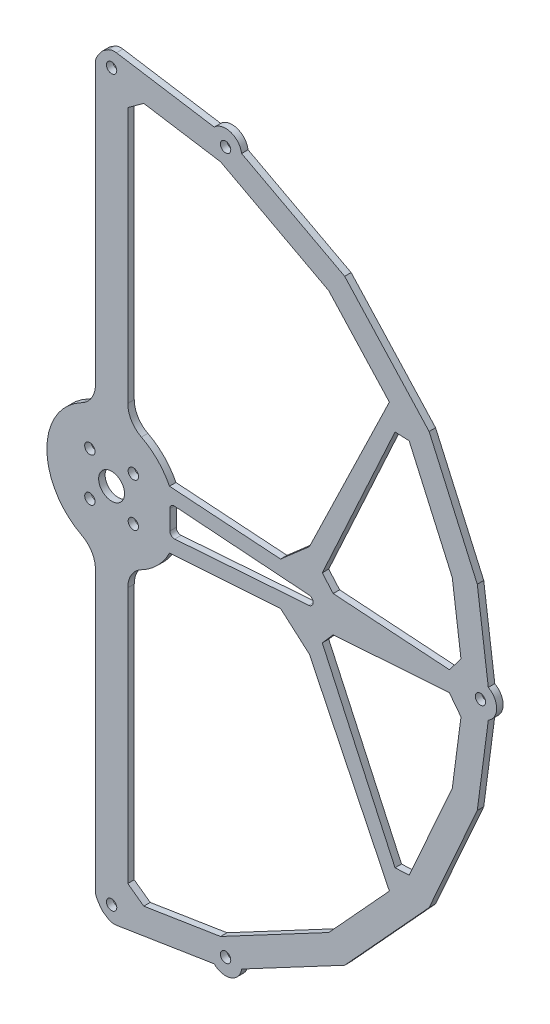
SolidWorks part; units mm, degrees
material "碳纤维板_1600kg_m3"
ref_plane "前视基准面" through (0, 0, 0) normal (0, 0, 1) x (1, 0, 0)
ref_plane "上视基准面" through (0, 0, 0) normal (0, 1, 0) x (1, 0, 0)
ref_plane "右视基准面" through (0, 0, 0) normal (1, 0, 0) x (0, 0, -1)
other "Configuration Table"
sketch "草图1" plane through (0, 0, 0) normal (0, 0, 1) x (1, 0, 0)
  line L0 (0, -115) -> (35.537, -109.3715)
  line L1 (35.537, -109.3715) -> (70.8011, -90.6212)
  line L2 (70.8011, -90.6212) -> (96.4471, -62.6335)
  line L3 (96.4471, -62.6335) -> (111.0815, -29.7642)
  line L4 (111.0815, -29.7642) -> (115, 0)
  line L5 (115, 0) -> (111.0815, 29.7642)
  line L6 (111.0815, 29.7642) -> (96.4471, 62.6335)
  line L7 (96.4471, 62.6335) -> (70.8011, 90.6212)
  line L8 (70.8011, 90.6212) -> (35.537, 109.3715)
  line L9 (35.537, 109.3715) -> (0, 115)
  line L10 (0, 115) -> (0, 111)
  line L11 (0, 111) -> (34.3009, 105.5673)
  line L12 (34.3009, 105.5673) -> (68.3384, 87.4692)
  line L13 (68.3384, 87.4692) -> (93.0924, 60.4549)
  line L14 (93.0924, 60.4549) -> (107.2178, 28.7289)
  line L15 (107.2178, 28.7289) -> (111, 0)
  line L16 (111, 0) -> (107.2178, -28.7289)
  line L17 (107.2178, -28.7289) -> (93.0924, -60.4549)
  line L18 (93.0924, -60.4549) -> (68.3384, -87.4692)
  line L19 (68.3384, -87.4692) -> (34.3009, -105.5673)
  line L20 (34.3009, -105.5673) -> (0, -111)
  line L21 (0, -111) -> (0, -115)
extrude "180度裁切侧框" add sketch "草图1" along normal blind 8
sketch "草图2" plane through (0, 0, 0) normal (0, 0, 1) x (1, 0, 0)
  line L0 (35.585, -103.0471) -> (37.4391, -108.7535)
  line L1 (37.4391, -108.7535) -> (33.6348, -109.9895)
  line L2 (33.6348, -109.9895) -> (31.7807, -104.2832)
  line L3 (31.7807, -104.2832) -> (35.585, -103.0471)
  line L4 (109, 2) -> (115, 2)
  line L5 (115, 2) -> (115, -2)
  line L6 (115, -2) -> (109, -2)
  line L7 (109, -2) -> (109, 2)
  line L8 (31.7807, 104.2832) -> (33.6348, 109.9895)
  line L9 (33.6348, 109.9895) -> (37.4391, 108.7535)
  line L10 (37.4391, 108.7535) -> (35.585, 103.0471)
  line L11 (35.585, 103.0471) -> (31.7807, 104.2832)
extrude "三个侧向支承" add sketch "草图2" along normal blind 36 from offset 8
sketch "草图3" plane through (0, 0, 0) normal (0, 0, 1) x (1, 0, 0)
  line L0 (0, -115) -> (35.537, -109.3715)
  line L1 (35.537, -109.3715) -> (70.8011, -90.6212)
  line L2 (70.8011, -90.6212) -> (96.4471, -62.6335)
  line L3 (96.4471, -62.6335) -> (111.0815, -29.7642)
  line L4 (111.0815, -29.7642) -> (115, 0)
  line L5 (115, 0) -> (111.0815, 29.7642)
  line L6 (111.0815, 29.7642) -> (96.4471, 62.6335)
  line L7 (96.4471, 62.6335) -> (70.8011, 90.6212)
  line L8 (70.8011, 90.6212) -> (35.537, 109.3715)
  line L9 (35.537, 109.3715) -> (0, 115)
  line L10 (0, 115) -> (0, 109)
  line L11 (0, 109) -> (33.6829, 103.6652)
  line L12 (33.6829, 103.6652) -> (67.1071, 85.8932)
  line L13 (67.1071, 85.8932) -> (91.4151, 59.3657)
  line L14 (91.4151, 59.3657) -> (105.2859, 28.2113)
  line L15 (105.2859, 28.2113) -> (109, 0)
  line L16 (109, 0) -> (105.2859, -28.2113)
  line L17 (105.2859, -28.2113) -> (91.4151, -59.3657)
  line L18 (91.4151, -59.3657) -> (67.1071, -85.8932)
  line L19 (67.1071, -85.8932) -> (33.6829, -103.6652)
  line L20 (33.6829, -103.6652) -> (0, -109)
  line L21 (0, -109) -> (0, -115)
extrude "180度裁切上框" add sketch "草图3" along normal blind 3 from offset 44
sketch "草图4" plane through (0, 0, 0) normal (0, 0, 1) x (1, 0, 0)
  circle A0 centre (0, 0) radius 20
  circle A1 centre (0, 0) radius 4
extrude "旧式圆根电机安装座" add sketch "草图4" along normal blind 3 from offset 44 separate body
sketch "草图5" plane through (0, 0, 0) normal (0, 0, 1) x (1, 0, 0)
  line L0 (17, -9) -> (113, -2.5)
  line L1 (113, -2.5) -> (113, 2.5)
  line L2 (113, 2.5) -> (17, 9)
  line L3 (17, 9) -> (17, -9)
  point P4 (0, 0)
extrude "旧式渐窄中梁" add sketch "草图5" along normal blind 3 from offset 44
sketch "草图6" plane through (0, 0, 0) normal (0, 0, 1) x (1, 0, 0)
  line L4 (-5, -112) -> (5, -112)
  line L5 (5, -112) -> (5, -16)
  line L6 (5, -16) -> (-5, -16)
  line L7 (-5, -16) -> (-5, -112)
extrude "旧式直斜侧梁_-1" add sketch "草图6" along normal blind 3 from offset 44
sketch "草图7" plane through (0, 0, 0) normal (0, 0, 1) x (1, 0, 0)
  line L0 (60.2133, 1.2799) -> (91.2349, -66.2401)
  line L1 (91.2349, -66.2401) -> (87.1651, -68.1599)
  line L2 (87.1651, -68.1599) -> (54.7867, -1.2799)
  line L3 (54.7867, -1.2799) -> (60.2133, 1.2799)
extrude "旧式Y形分叉_-1" add sketch "草图7" along normal blind 3 from offset 44
sketch "草图8" plane through (0, 0, 0) normal (0, 0, 1) x (1, 0, 0)
  line L4 (-5, 16) -> (5, 16)
  line L5 (5, 16) -> (5, 112)
  line L6 (5, 112) -> (-5, 112)
  line L7 (-5, 112) -> (-5, 16)
extrude "旧式直斜侧梁_1" add sketch "草图8" along normal blind 3 from offset 44
sketch "草图9" plane through (0, 0, 0) normal (0, 0, 1) x (1, 0, 0)
  line L0 (54.7867, 1.2799) -> (87.1651, 68.1599)
  line L1 (87.1651, 68.1599) -> (91.2349, 66.2401)
  line L2 (91.2349, 66.2401) -> (60.2133, -1.2799)
  line L3 (60.2133, -1.2799) -> (54.7867, 1.2799)
extrude "旧式Y形分叉_1" add sketch "草图9" along normal blind 3 from offset 44
sketch "草图10" plane through (0, 0, 0) normal (0, 0, 1) x (1, 0, 0)
  line L0 (18, -4.5) -> (18, 4.5)
  line L1 (18, 4.5) -> (80.33, 0)
  line L2 (80.33, 0) -> (18, -4.5)
extrude "旧式中梁三角镂空" cut sketch "草图10" along normal blind 3 from offset 44
sketch "草图11" plane through (0, 0, 0) normal (0, 0, 1) x (1, 0, 0)
  line L0 (-5, -107) -> (5, -107)
  line L1 (5, -107) -> (5, -116.2081)
  line L2 (5, -116.2081) -> (0, -117)
  line L3 (0, -117) -> (-3, -115)
  line L4 (-3, -115) -> (-5, -112)
  line L5 (-5, -112) -> (-5, -107)
  line L6 (-5, 107) -> (5, 107)
  line L7 (5, 107) -> (5, 116.2081)
  line L8 (5, 116.2081) -> (0, 117)
  line L9 (0, 117) -> (-3, 115)
  line L10 (-3, 115) -> (-5, 112)
  line L11 (-5, 112) -> (-5, 107)
extrude "上连接耳座" add sketch "草图11" along normal blind 3 from offset 44
sketch "草图12" plane through (0, 0, 0) normal (0, 0, 1) x (1, 0, 0)
  circle A0 centre (0, 112) radius 5
  circle A1 centre (0, -112) radius 5
extrude "下连接耳座" add sketch "草图12" along normal blind 8
sketch "草图13" plane through (0, 0, 0) normal (0, 0, 1) x (1, 0, 0)
  circle A4 centre (0, 112) radius 1.6
  circle A5 centre (0, -112) radius 1.6
  circle A6 centre (-6.7175, -6.7175) radius 1.6
  circle A7 centre (-6.7175, 6.7175) radius 1.6
  circle A8 centre (6.7175, -6.7175) radius 1.6
  circle A9 centre (6.7175, 6.7175) radius 1.6
extrude "电机及上连接孔" cut sketch "草图13" along normal blind 3 from offset 44
sketch "草图14" plane through (0, 0, 0) normal (0, 0, 1) x (1, 0, 0)
  circle A0 centre (0, 112) radius 1.6
  circle A1 centre (0, -112) radius 1.6
extrude "下连接孔" cut sketch "草图14" along normal blind 8
sketch "草图15" plane through (0, 0, 0) normal (0, 0, 1) x (1, 0, 0)
  line L0 (-300, -300) -> (300, -300)
  line L1 (300, -300) -> (300, 300)
  line L2 (300, 300) -> (-300, 300)
  line L3 (-300, 300) -> (-300, -300)
extrude "上下拆分_仅保留上层" cut sketch "草图15" along normal blind 44
sketch "草图16" plane through (0, 0, 0) normal (0, 0, 1) x (1, 0, 0)
  line L0 (0, -117) -> (36.155, -111.2736)
  line L1 (36.155, -111.2736) -> (72.0324, -92.1973)
  line L2 (72.0324, -92.1973) -> (98.1245, -63.7228)
  line L3 (98.1245, -63.7228) -> (113.0133, -30.2818)
  line L4 (113.0133, -30.2818) -> (117, 0)
  line L5 (117, 0) -> (113.0133, 30.2818)
  line L6 (113.0133, 30.2818) -> (98.1245, 63.7228)
  line L7 (98.1245, 63.7228) -> (72.0324, 92.1973)
  line L8 (72.0324, 92.1973) -> (36.155, 111.2736)
  line L9 (36.155, 111.2736) -> (0, 117)
  line L10 (0, 117) -> (0, 114)
  line L11 (0, 114) -> (35.2279, 108.4204)
  line L12 (35.2279, 108.4204) -> (70.1854, 89.8332)
  line L13 (70.1854, 89.8332) -> (95.6084, 62.0888)
  line L14 (95.6084, 62.0888) -> (110.1155, 29.5054)
  line L15 (110.1155, 29.5054) -> (114, 0)
  line L16 (114, 0) -> (110.1155, -29.5054)
  line L17 (110.1155, -29.5054) -> (95.6084, -62.0888)
  line L18 (95.6084, -62.0888) -> (70.1854, -89.8332)
  line L19 (70.1854, -89.8332) -> (35.2279, -108.4204)
  line L20 (35.2279, -108.4204) -> (0, -114)
  line L21 (0, -114) -> (0, -117)
extrude "外圈径向加厚2mm" add sketch "草图16" along normal blind 3 from offset 44
sketch "草图17" plane through (0, 0, 0) normal (0, 0, 1) x (1, 0, 0)
  circle A0 centre (35.2279, -108.4204) radius 5
extrude "M3铝柱上定位耳" add sketch "草图17" along normal blind 3 from offset 44
sketch "草图18" plane through (0, 0, 0) normal (0, 0, 1) x (1, 0, 0)
  circle A0 centre (114, 0) radius 5
extrude "凸台-拉伸3" add sketch "草图18" along normal blind 3 from offset 44
sketch "草图19" plane through (0, 0, 0) normal (0, 0, 1) x (1, 0, 0)
  circle A0 centre (35.2279, 108.4204) radius 5
extrude "凸台-拉伸4" add sketch "草图19" along normal blind 3 from offset 44
sketch "草图20" plane through (0, 0, 0) normal (0, 0, 1) x (1, 0, 0)
  circle A0 centre (35.2279, -108.4204) radius 1.6
  circle A1 centre (114, 0) radius 1.6
  circle A2 centre (35.2279, 108.4204) radius 1.6
extrude "三处M3上层固定孔" cut sketch "草图20" along normal blind 3 from offset 44
fillet "外侧梁根部圆角_R7p8_参考75度桨保" radius 7.8 4 edges at (5, 19.3649, 45.5) (-5, 19.3649, 45.5) (5, -19.3649, 45.5) (-5, -19.3649, 45.5)
fillet "端耳外缘圆角_R3p9_轮廓内收" radius 3.9 6 edges at (0, 117, 45.5) (-3, 115, 45.5) (0, -117, 45.5) (-3, -115, 45.5) (-5, 112, 45.5) (-5, -112, 45.5)
sketch "草图21" plane through (0, 0, 0) normal (0, 0, 1) x (1, 0, 0)
  line L0 (-300, -300) -> (300, -300)
  line L1 (300, -300) -> (300, 300)
  line L2 (300, 300) -> (-300, 300)
  line L3 (-300, 300) -> (-300, -300)
extrude "统一2mm板厚_上层保留45至47" cut sketch "草图21" along normal blind 1 from offset 44
fillet "圆角1" radius 1.4 3 edges at (18, -4.5, 46) (80.33, 0, 46) (18, 4.5, 46)
chamfer "倒角1" distance 5 angle 45 10 edges at (108.6319, -2.7958, 46) (108.6319, 2.7958, 46) (89.1915, -61.7923, 46) (89.1915, 61.7923, 46) (5, -108.2081, 46) (5, 108.2081, 46) (63.4901, 5.8522, 46) (63.4901, -5.8522, 46) (57.2063, -6.2777, 46) (57.2063, 6.2777, 46)
